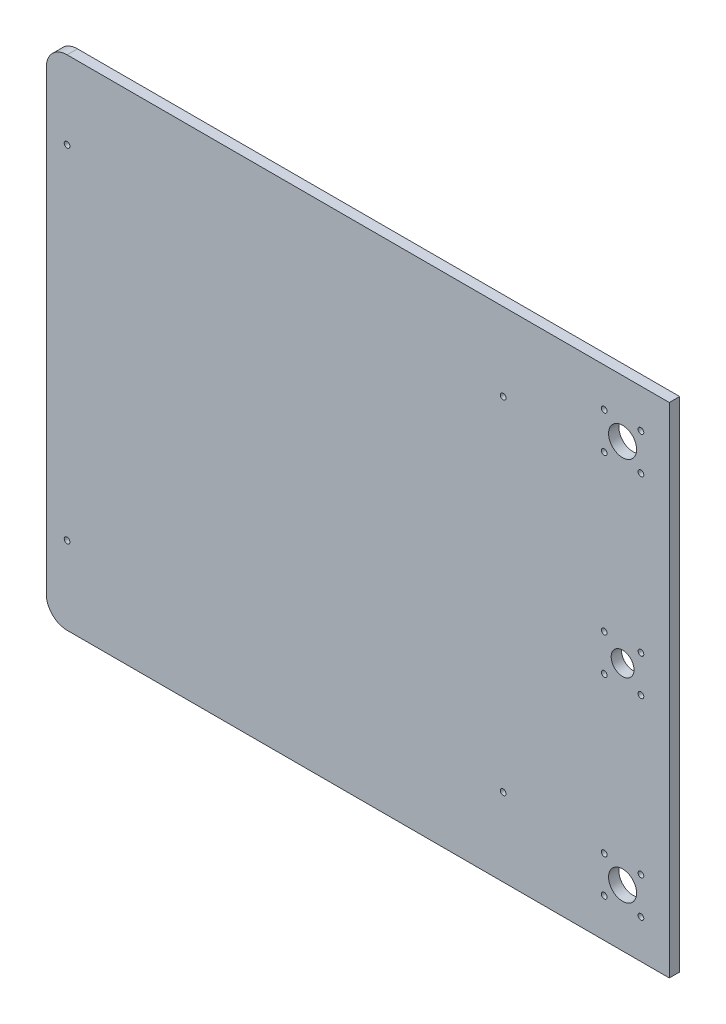
SolidWorks part; units mm, degrees
material "АД1 ГОСТ 4784-97"
ref_plane "Спереди" through (0, 0, 0) normal (0, 0, 1) x (1, 0, 0)
ref_plane "Сверху" through (0, 0, 0) normal (0, 1, 0) x (1, 0, 0)
ref_plane "Справа" through (0, 0, 0) normal (1, 0, 0) x (0, 0, -1)
ref_axis "ОсьX" through (-88.99, 0, 0) along (1, 0, 0)
ref_axis "ОсьZ" through (0, 55, 0) along (0, -1, 0)
ref_axis "ОсьY" through (0, 0, -88.99) along (0, 0, 1)
sketch "Эскиз1" plane through (0, 0, 0) normal (0, 0, 1) x (1, 0, 0)
  line L0 (0, 0) -> (0, 59.9562) construction
  line L1 (-555, 240) -> (45, 240)
  line L2 (-555, 240) -> (-555, -240)
  line L3 (-555, -240) -> (45, -240)
  line L4 (45, 240) -> (45, -240)
  line L5 (-17.6777, 17.6777) -> (0, 0) construction
  line L6 (-555, 240) -> (-555, -240)
  line L7 (45, 240) -> (45, -240)
  line L8 (-109.4093, 0) -> (189.9089, 0) construction
  line L9 (0, 0) -> (0, 25) construction
  line L10 (-17.6777, 202.6777) -> (0, 185) construction
  line L11 (0, 185) -> (0, 210) construction
  circle A24 centre (0, 0) radius 11
  circle A25 centre (0, 0) radius 25 construction
  circle A26 centre (-17.6777, 17.6777) radius 2.75
  circle A27 centre (17.6777, 17.6777) radius 2.75
  circle A28 centre (-17.6777, -17.6777) radius 2.75
  circle A29 centre (17.6777, -17.6777) radius 2.75
  circle A30 centre (0, 185) radius 13.5
  circle A32 centre (0, 185) radius 25 construction
  circle A33 centre (-17.6777, 167.3223) radius 2.75
  circle A34 centre (17.6777, 167.3223) radius 2.75
  circle A35 centre (17.6777, 202.6777) radius 2.75
  circle A36 centre (-17.6777, 202.6777) radius 2.75
  circle A37 centre (-17.6777, -202.6777) radius 2.75
  circle A38 centre (17.6777, -202.6777) radius 2.75
  circle A39 centre (17.6777, -167.3223) radius 2.75
  circle A40 centre (-17.6777, -167.3223) radius 2.75
  circle A41 centre (0, -185) radius 25 construction
  circle A42 centre (0, -185) radius 13.5
  circle A43 centre (-535, 165) radius 2.75
  circle A44 centre (-115, 165) radius 2.75
  circle A45 centre (-115, -165) radius 2.75
  circle A46 centre (-535, -165) radius 2.75
  point P6 (-555, 0)
  dimension "D3" = 370
  dimension "D4" = 27
  dimension "D5" = 45
  dimension "D6" = 5.5
  dimension "D8" = 20
  dimension "D13" = 22
  dimension "D14" = 50
  dimension "D15" = 5.5
  dimension "D18" = 5.5
  dimension "D19" = 50
  dimension "D9" = 330
  dimension "D1" = 600
  dimension "D2" = 480
  dimension "D7" = 420
  dimension "D12" = 45
  dimension "D16" = 45
extrude "Бобышка-Вытянуть1" add sketch "Эскиз1" along normal blind 10 contours L4 L1 L2 L3 region at (-256.5903, 0, 0)
fillet "Скругление1" radius 20 2 edges at (-555, 240, 5) (-555, -240, 5)
